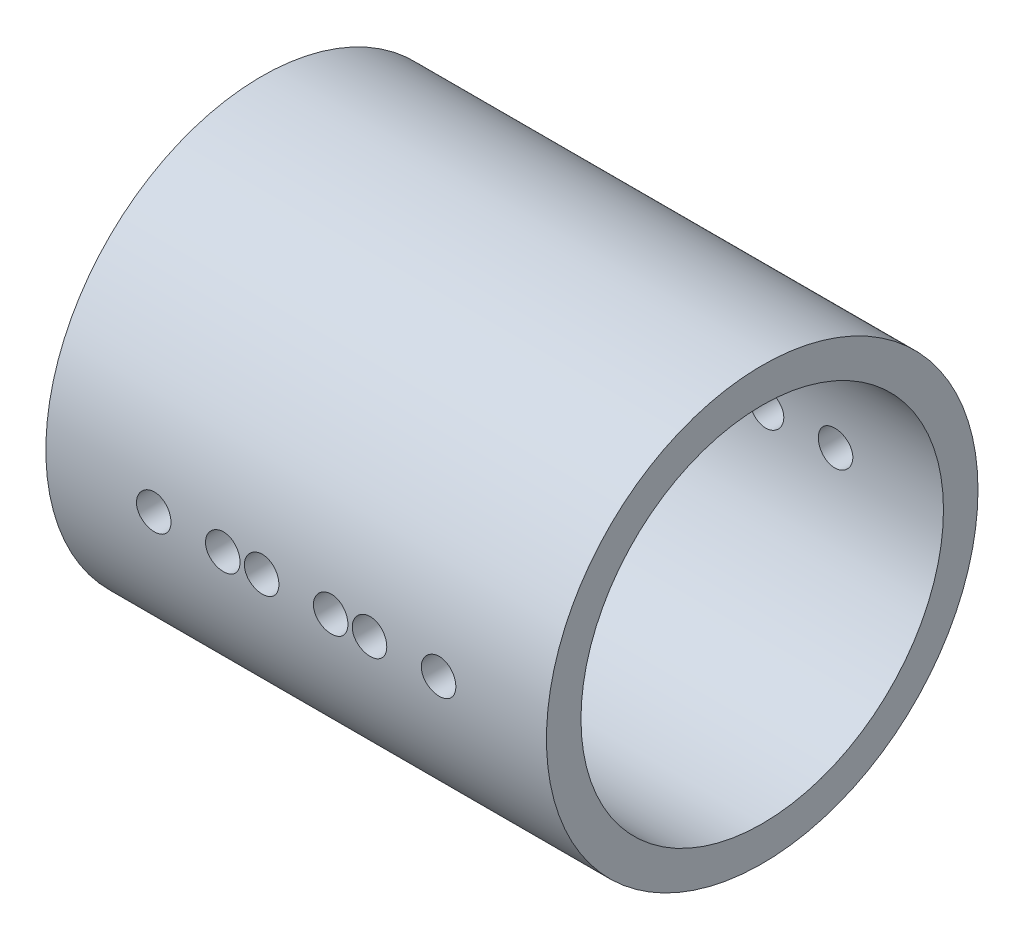
SolidWorks part; units mm, degrees
material "Zoltek Panex 33"
ref_plane "Спереди" through (0, 0, 0) normal (0, 0, 1) x (1, 0, 0)
ref_plane "Сверху" through (0, 0, 0) normal (0, 1, 0) x (1, 0, 0)
ref_plane "Справа" through (0, 0, 0) normal (1, 0, 0) x (0, 0, -1)
other "Configuration Table"
sketch "Эскиз2" plane through (0, 0, 0) normal (1, 0, 0) x (0, 0, -1)
  circle A0 centre (0, 0) radius 25
  circle A1 centre (0, 0) radius 21
  dimension "D1" = 50
  dimension "D2" = 42
extrude "Бобышка-Вытянуть2" add sketch "Эскиз2" along normal blind 58
ref_plane "Плоскость1" through (0, 0, 25) normal (0, 0, 1) x (1, 0, 0)
sketch "Эскиз4" plane through (0, 0, 25) normal (0, 0, 1) x (1, 0, 0)
  line L0 (0, -25) -> (58, -25) construction
  line L1 (58, -25) -> (58, 25) construction
  circle A0 centre (12.5, 0) radius 2
  circle A1 centre (45.5, 0) radius 2
  circle A2 centre (25, 0) radius 2
  circle A3 centre (37.5, 0) radius 2
  circle A4 centre (33, 0) radius 2
  circle A5 centre (20.5, 0) radius 2
  dimension "D1" = 4
  dimension "D4" = 4
  dimension "D6" = 4
  dimension "D8" = 4
  dimension "D10" = 4
  dimension "D11" = 4
  dimension "D2" = 12.5
  dimension "D3" = 25
  dimension "D5" = 12.5
  dimension "D7" = 12.5
  dimension "D9" = 12.5
  dimension "15" = 12.5
  dimension "D12" = 12.5
extrude "Вырез-Вытянуть2" cut sketch "Эскиз4" against normal through all and the other way blind 10 contours A0 | A1 | A2 | A3 | A5 | A4
equation "\"Diameter\"= 50мм"
equation "\"D1@Эскиз2\"= \"Diameter\""
equation "\"Length\" = 58мм"
equation "\"Thickness\"= 4мм"
equation "\"D1@Бобышка-Вытянуть2\"= \"Length\""
equation "\"D2@Эскиз2\" = \"Diameter\" - \"Thickness\" * 2"
equation "\"D4@Эскиз4\"=\"D1@Эскиз4\""
equation "\"D5@Эскиз4\"=\"D2@Эскиз4\""
equation "\"D3@Эскиз4\"=\"Diameter\"/2"
equation "\"D6@Эскиз4\"=\"D1@Эскиз4\""
equation "\"D8@Эскиз4\"=\"D6@Эскиз4\""
equation "\"D10@Эскиз4\"=\"D4@Эскиз4\""
equation "\"D11@Эскиз4\"=\"D4@Эскиз4\""
equation "\"D9@Эскиз4\"=\"D7@Эскиз4\""
